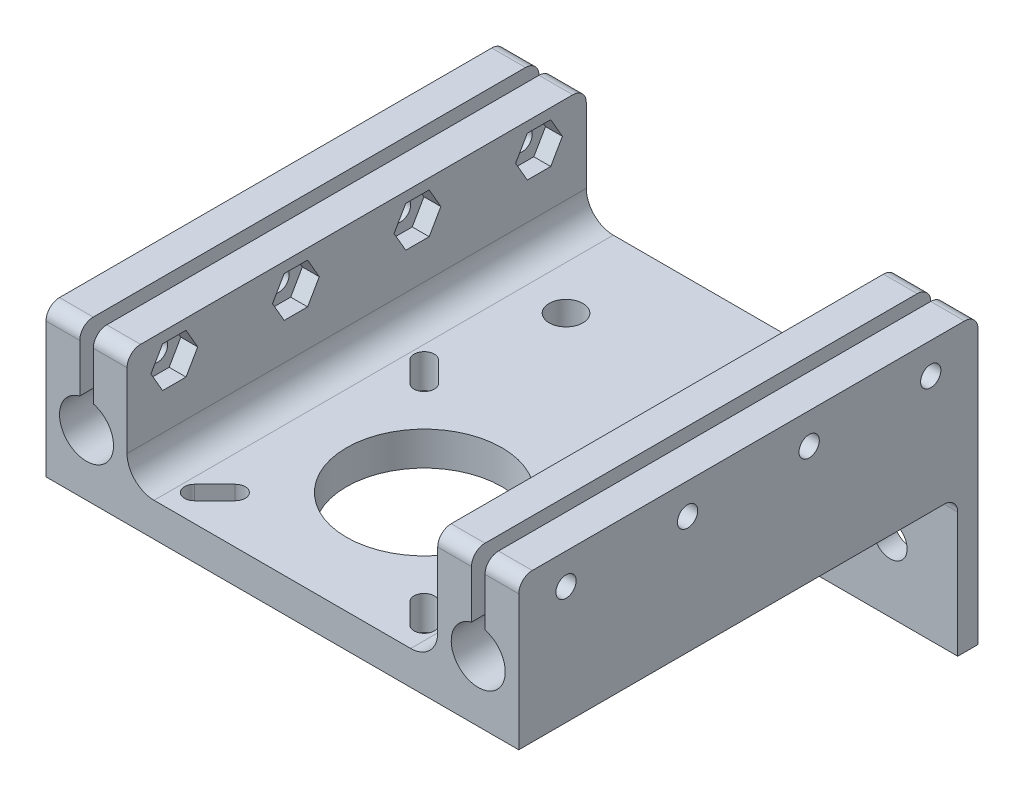
SolidWorks part; units mm, degrees
ref_plane "Front Plane" through (0, 0, 0) normal (0, 0, 1) x (1, 0, 0)
ref_plane "Top Plane" through (0, 0, 0) normal (0, 1, 0) x (1, 0, 0)
ref_plane "Right Plane" through (0, 0, 0) normal (1, 0, 0) x (0, 0, -1)
sketch "Sketch1" plane through (0, 0, 0) normal (0, 0, 1) x (1, 0, 0)
  line L0 (-25, -2.75) -> (25, -2.75) construction
  line L1 (-35, 12.75) -> (35, 12.75)
  line L2 (-35, 12.75) -> (-35, -12.75)
  line L3 (-35, -12.75) -> (35, -12.75)
  line L4 (35, 12.75) -> (35, -12.75)
  line L5 (-35, 12.75) -> (35, -12.75) construction
  line L6 (-35, -12.75) -> (35, 12.75) construction
  line L7 (0, -12.75) -> (0, 12.75) construction
  circle A0 centre (-25, -2.75) radius 2.5
  circle A1 centre (25, -2.75) radius 2.5
  circle A2 centre (0, -2.75) radius 2.5
  point P0 (0, 0)
  point P10 (0, -2.75)
  dimension "D5" = 5
  dimension "D1" = 70
  dimension "D2" = 25.5
  dimension "D3" = 10
  dimension "D4" = 50
extrude "Boss-Extrude1" add sketch "Sketch1" along normal blind 3
sketch "Sketch2" plane through (0, 0, 0) normal (0, 0, 1) x (1, 0, 0)
  line L0 (35, -12.75) -> (35, 12.75) construction
  line L1 (-19, 12.75) -> (35, 12.75) construction
  line L2 (-35, 12.75) -> (-35, 7.75) construction
  line L3 (-35, 7.75) -> (35, 7.75)
  line L4 (35, 12.75) -> (35, 7.75) construction
  line L5 (-19, 12.75) -> (19, 12.75)
  line L6 (-35, 7.75) -> (-35, 29.75)
  line L7 (-35, 12.75) -> (-35, 29.75) construction
  line L8 (-35, 29.75) -> (-23, 29.75)
  line L9 (-23, 16.75) -> (-23, 29.75)
  line L10 (35, 29.75) -> (35, 7.75)
  line L11 (35, 12.75) -> (35, 29.75) construction
  line L12 (35, 29.75) -> (23, 29.75)
  line L13 (23, 16.75) -> (23, 29.75)
  line L14 (35, 12.75) -> (-35, 12.75) construction
  line L15 (-35, 12.75) -> (-35, -12.75) construction
  line L16 (0, -12.75) -> (0, 29.75) construction
  line L17 (-35, -12.75) -> (35, -12.75) construction
  line L18 (-29, 16.75) -> (29, 16.75) construction
  line L19 (-29, 29.75) -> (-29, 16.75) construction
  arc A0 (-19, 12.75) -> (-23, 16.75) centre (-19, 16.75) cw
  arc A1 (23, 16.75) -> (19, 12.75) centre (19, 16.75) cw
  circle A2 centre (-29, 16.75) radius 4
  circle A3 centre (29, 16.75) radius 4
  point P27 (0, 16.75)
  dimension "D1" = 4
  dimension "D3" = 4
  dimension "D6" = 58
  dimension "D7" = 8
  dimension "D2" = 12
  dimension "D4" = 5
  dimension "D5" = 17
extrude "Boss-Extrude2" add sketch "Sketch2" along normal blind 68
sketch "Sketch3" plane through (0, 0, 0) normal (0, 0, 1) x (1, 0, 0)
  line L0 (-30, 29.75) -> (-30, 16.75)
  line L1 (-30, 29.75) -> (-28, 29.75)
  line L2 (-30, 16.75) -> (-28, 16.75)
  line L3 (-28, 29.75) -> (-28, 16.75)
  line L4 (-30, 29.75) -> (-28, 16.75) construction
  line L5 (-30, 16.75) -> (-28, 29.75) construction
  line L6 (-29, 29.75) -> (-29, 16.75) construction
  line L7 (-35, 29.75) -> (-23, 29.75) construction
  line L8 (29, 29.75) -> (29, 16.75) construction
  line L9 (35, 29.75) -> (23, 29.75) construction
  line L10 (28, 29.75) -> (28, 16.75)
  line L11 (28, 29.75) -> (30, 29.75)
  line L12 (28, 16.75) -> (30, 16.75)
  line L13 (30, 29.75) -> (30, 16.75)
  line L14 (28, 29.75) -> (30, 16.75) construction
  line L15 (28, 16.75) -> (30, 29.75) construction
  point P1 (-29, 23.25)
  point P16 (29, 23.25)
  dimension "D1" = 2
extrude "Cut-Extrude3" cut sketch "Sketch3" along normal through all
fillet "Fillet1" radius 2 1 edges at (0, 7.75, 3)
sketch "Sketch4" plane through (0, 7.75, 0) normal (0, -1, 0) x (1, 0, 0)
  line L0 (-12.5, 13.5) -> (12.5, 13.5) construction
  line L3 (-35, 3) -> (35, 3) construction
  circle A0 centre (-12.5, 13.5) radius 2.5
  circle A1 centre (12.5, 13.5) radius 2.5
  point P2 (0, 13.5)
  dimension "D3" = 5
  dimension "D1" = 10.5
  dimension "D2" = 25
extrude "Cut-Extrude4" cut sketch "Sketch4" against normal through all
sketch "Sketch5" plane through (0, 12.75, 0) normal (0, 1, 0) x (1, 0, 0)
  line L0 (19, -68) -> (-19, -68) construction
  line L1 (0, -68) -> (0, -26) construction
  line L2 (-21, -47) -> (21, -47) construction
  line L3 (-17, -30) -> (-14, -33) construction
  line L4 (-14, -33) -> (14, -33) construction
  line L5 (-14, -33) -> (-14, -61) construction
  line L6 (-14, -61) -> (14, -61) construction
  line L7 (14, -33) -> (14, -61) construction
  line L8 (-14, -33) -> (14, -61) construction
  line L9 (-14, -61) -> (14, -33) construction
  line L10 (-17, -30) -> (17, -30) construction
  line L11 (-17, -30) -> (-17, -64) construction
  line L12 (-17, -64) -> (17, -64) construction
  line L13 (17, -30) -> (17, -64) construction
  line L14 (-17, -30) -> (17, -64) construction
  line L15 (-17, -64) -> (17, -30) construction
  line L16 (-15.9393, -28.9393) -> (-12.9393, -31.9393)
  line L17 (-18.0607, -31.0607) -> (-15.0607, -34.0607)
  line L18 (14, -33) -> (17, -30) construction
  line L19 (12.9393, -31.9393) -> (15.9393, -28.9393)
  line L20 (15.0607, -34.0607) -> (18.0607, -31.0607)
  line L21 (17, -64) -> (14, -61) construction
  line L22 (15.9393, -65.0607) -> (12.9393, -62.0607)
  line L23 (18.0607, -62.9393) -> (15.0607, -59.9393)
  line L24 (-14, -61) -> (-17, -64) construction
  line L25 (-12.9393, -62.0607) -> (-15.9393, -65.0607)
  line L26 (-15.0607, -59.9393) -> (-18.0607, -62.9393)
  circle A0 centre (0, -47) radius 11.5
  arc A1 (-15.9393, -28.9393) -> (-18.0607, -31.0607) centre (-17, -30) ccw
  arc A2 (-15.0607, -34.0607) -> (-12.9393, -31.9393) centre (-14, -33) ccw
  arc A3 (12.9393, -31.9393) -> (15.0607, -34.0607) centre (14, -33) ccw
  arc A4 (18.0607, -31.0607) -> (15.9393, -28.9393) centre (17, -30) ccw
  arc A5 (15.9393, -65.0607) -> (18.0607, -62.9393) centre (17, -64) ccw
  arc A6 (15.0607, -59.9393) -> (12.9393, -62.0607) centre (14, -61) ccw
  arc A7 (-12.9393, -62.0607) -> (-15.0607, -59.9393) centre (-14, -61) ccw
  arc A8 (-18.0607, -62.9393) -> (-15.9393, -65.0607) centre (-17, -64) ccw
  point P7 (0, -47)
  point P17 (-15.5, -31.5)
  point P22 (15.5, -31.5)
  point P27 (15.5, -62.5)
  point P32 (-15.5, -62.5)
  dimension "D3" = 23
  dimension "D1" = 42
  dimension "D2" = 42
  dimension "D4" = 28
  dimension "D5" = 34
  dimension "D6" = 3
extrude "Cut-Extrude5" cut sketch "Sketch5" against normal through all
sketch "Sketch6" plane through (-35, 0, 0) normal (-1, 0, 0) x (0, 0, 1)
  line L0 (7, 25.1865) -> (61, 25.1865) construction
  line L3 (68, 29.75) -> (0, 29.75) construction
  line L4 (34, 29.75) -> (34, 7.75) construction
  line L5 (68, 7.75) -> (5, 7.75) construction
  line L6 (7, 29.75) -> (7, 20.623) construction
  line L7 (0, 20.623) -> (68, 20.623) construction
  circle A0 centre (7, 25.1865) radius 1.5
  circle A1 centre (25, 25.1865) radius 1.5
  circle A2 centre (43, 25.1865) radius 1.5
  circle A3 centre (61, 25.1865) radius 1.5
  point P8 (34, 25.1865)
  point P19 (7, 25.1865)
  dimension "D2" = 3
  dimension "D3" = 18
  dimension "D4" = 18
  dimension "D5" = 18
extrude "Cut-Extrude6" cut sketch "Sketch6" against normal through all
sketch "Sketch7" plane through (-23, 0, 0) normal (1, 0, 0) x (0, 0, -1)
  line L0 (-68, 29.75) -> (0, 29.75) construction
  line L1 (-59.2679, 22.1865) -> (-57.5359, 25.1865)
  line L2 (-57.5359, 25.1865) -> (-59.2679, 28.1865)
  line L3 (-59.2679, 28.1865) -> (-62.7321, 28.1865)
  line L4 (-62.7321, 28.1865) -> (-64.4641, 25.1865)
  line L5 (-64.4641, 25.1865) -> (-62.7321, 22.1865)
  line L6 (-62.7321, 22.1865) -> (-59.2679, 22.1865)
  line L8 (-41.2679, 22.1865) -> (-39.5359, 25.1865)
  line L9 (-39.5359, 25.1865) -> (-41.2679, 28.1865)
  line L10 (-41.2679, 28.1865) -> (-44.7321, 28.1865)
  line L11 (-44.7321, 28.1865) -> (-46.4641, 25.1865)
  line L12 (-46.4641, 25.1865) -> (-44.7321, 22.1865)
  line L13 (-44.7321, 22.1865) -> (-41.2679, 22.1865)
  line L14 (-23.2679, 22.1865) -> (-21.5359, 25.1865)
  line L15 (-21.5359, 25.1865) -> (-23.2679, 28.1865)
  line L16 (-23.2679, 28.1865) -> (-26.7321, 28.1865)
  line L17 (-26.7321, 28.1865) -> (-28.4641, 25.1865)
  line L18 (-28.4641, 25.1865) -> (-26.7321, 22.1865)
  line L19 (-26.7321, 22.1865) -> (-23.2679, 22.1865)
  line L20 (-5.2679, 22.1865) -> (-3.5359, 25.1865)
  line L21 (-3.5359, 25.1865) -> (-5.2679, 28.1865)
  line L22 (-5.2679, 28.1865) -> (-8.7321, 28.1865)
  line L23 (-8.7321, 28.1865) -> (-10.4641, 25.1865)
  line L24 (-10.4641, 25.1865) -> (-8.7321, 22.1865)
  line L25 (-8.7321, 22.1865) -> (-5.2679, 22.1865)
  circle A0 centre (-61, 25.1865) radius 3 construction
  circle A1 centre (-43, 25.1865) radius 3 construction
  circle A2 centre (-25, 25.1865) radius 3 construction
  circle A3 centre (-7, 25.1865) radius 3 construction
  dimension "D1" = 6
extrude "Cut-Extrude7" cut sketch "Sketch7" along normal offset from surface (51 mm away) 2.5 from offset 2.5 up to face at (23, 25.1865, 59.5) offset beyond the face yes offset against normal yes
fillet "Fillet2" radius 2 8 edges at (32.5, 29.75, 0) (32.5, 29.75, 68) (25.5, 29.75, 0) (-25.5, 29.75, 0) (-32.5, 29.75, 0) (-32.5, 29.75, 68) (-25.5, 29.75, 68) (25.5, 29.75, 68)
equation "\"D4@Sketch6\"=\"D3@Sketch6\""
equation "\"D5@Sketch6\"=\"D3@Sketch6\""
